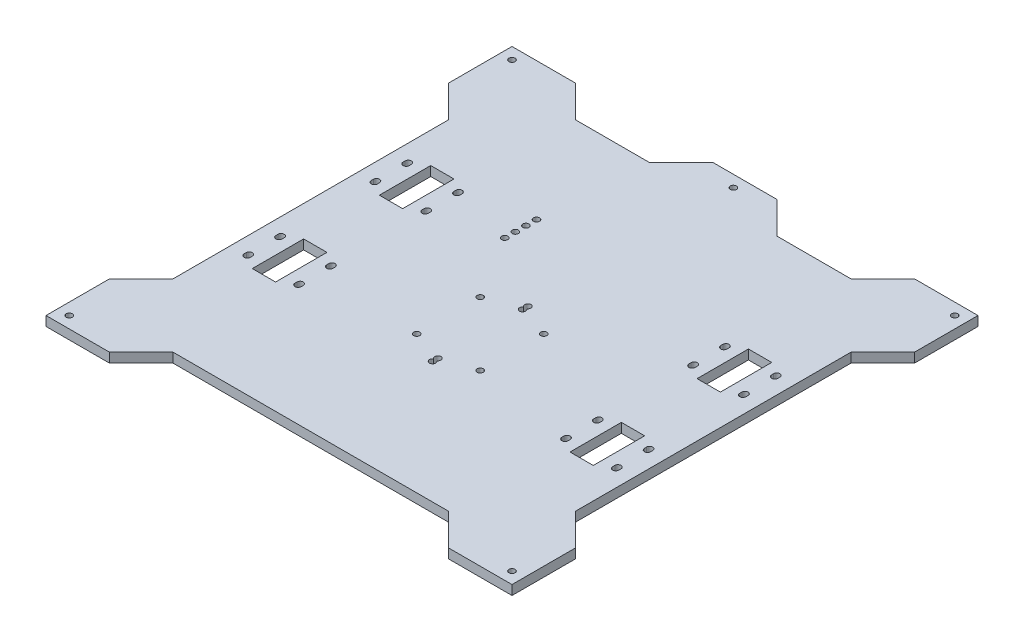
SolidWorks part; units mm, degrees
ref_plane "Front Plane" through (0, 0, 0) normal (0, 0, 1) x (1, 0, 0)
ref_plane "Top Plane" through (0, 0, 0) normal (0, 1, 0) x (1, 0, 0)
ref_plane "Right Plane" through (0, 0, 0) normal (1, 0, 0) x (0, 0, -1)
sketch "Sketch1" plane through (0, 0, 0) normal (0, 1, 0) x (1, 0, 0)
  line L1 (-110, 110) -> (110, 110)
  line L2 (-110, 110) -> (-110, -110)
  line L3 (-110, -110) -> (110, -110)
  line L4 (110, 110) -> (110, -110)
  line L5 (-110, 110) -> (110, -110) construction
  line L6 (-110, -110) -> (110, 110) construction
  point P0 (0, 0)
  dimension "D1" = 220
  dimension "D2" = 220
extrude "Square" add sketch "Sketch1" along normal blind 4.5
sketch "Sketch2" plane through (0, 4.5, 0) normal (0, 1, 0) x (1, 0, 0)
  line L0 (0, 110) -> (0, -110) construction
  line L1 (110, 110) -> (-110, 110) construction
  line L2 (-110, -110) -> (110, -110) construction
  line L3 (-110, 0) -> (110, 0) construction
  line L4 (-110, 110) -> (-110, -110) construction
  line L5 (110, -110) -> (110, 110) construction
  line L6 (75, 110) -> (75, -110) construction
  line L7 (75, 30) -> (0, 30) construction
  line L8 (75, -30) -> (0, -30) construction
  circle A0 centre (87, 38) radius 1.45
  circle A1 centre (87, 22) radius 1.45
  circle A2 centre (63, 22) radius 1.45
  circle A3 centre (63, 38) radius 1.45
  circle A4 centre (-63, 38) radius 1.45
  circle A5 centre (-63, 22) radius 1.45
  circle A6 centre (-87, 22) radius 1.45
  circle A7 centre (-87, 38) radius 1.45
  circle A8 centre (-87, 22) radius 1.45
  circle A9 centre (-87, 38) radius 1.45
  circle A10 centre (-63, 38) radius 1.45
  circle A11 centre (-63, 22) radius 1.45
  circle A12 centre (63, 22) radius 1.45
  circle A13 centre (63, 38) radius 1.45
  circle A14 centre (87, 38) radius 1.45
  circle A15 centre (87, 22) radius 1.45
  circle A16 centre (87, -22) radius 1.45
  circle A17 centre (87, -38) radius 1.45
  circle A18 centre (63, -38) radius 1.45
  circle A19 centre (63, -22) radius 1.45
  circle A20 centre (-63, -22) radius 1.45
  circle A21 centre (-63, -38) radius 1.45
  circle A22 centre (-87, -38) radius 1.45
  circle A23 centre (-87, -22) radius 1.45
  circle A24 centre (-87, -38) radius 1.45
  circle A25 centre (-87, -22) radius 1.45
  circle A26 centre (-63, -22) radius 1.45
  circle A27 centre (-63, -38) radius 1.45
  circle A28 centre (63, -38) radius 1.45
  circle A29 centre (63, -22) radius 1.45
  circle A30 centre (87, -22) radius 1.45
  circle A31 centre (87, -38) radius 1.45
  dimension "D6" = 2.9
  dimension "D7" = 2.9
  dimension "D1" = 75
  dimension "D2" = 30
  dimension "D3" = 16
  dimension "D5" = 12
extrude "LM8UU-Holders" cut sketch "Sketch2" against normal through all contours A7 | A6 | A5 | A4 | A20 | A21 | A22 | A23 | A19 | A18 | A17 | A16 | A1 | A0 | A3 | A2 region at (87, 4.5, -38) region at (87, 4.5, -22) region at (63, 4.5, -22) region at (63, 4.5, -38) region at (-63, 4.5, -38) region at (-63, 4.5, -22) region at (-87, 4.5, -22) region at (-87, 4.5, -38) region at (87, 4.5, 22) region at (87, 4.5, 38) region at (63, 4.5, 38) region at (63, 4.5, 22) region at (-63, 4.5, 22) region at (-63, 4.5, 38) region at (-87, 4.5, 38) region at (-87, 4.5, 22)
sketch "Sketch10" plane through (0, 4.5, 0) normal (0, 1, 0) x (1, 0, 0)
  line L0 (0, 110) -> (0, -79.9796) construction
  line L3 (-26.5242, 0) -> (110, 0) construction
  line L6 (75, 110) -> (75, -110) construction
  line L7 (75, 30) -> (-75, 30) construction
  line L8 (87, 22) -> (87, 23) construction
  line L9 (110, 110) -> (-110, 110) construction
  line L10 (110, -110) -> (110, 110) construction
  line L11 (85.55, 22) -> (85.55, 23)
  line L12 (88.45, 22) -> (88.45, 23)
  line L13 (87, 38) -> (87, 37) construction
  line L14 (88.45, 38) -> (88.45, 37)
  line L15 (85.55, 38) -> (85.55, 37)
  line L16 (63, 38) -> (63, 37) construction
  line L17 (61.55, 38) -> (61.55, 37)
  line L18 (64.45, 38) -> (64.45, 37)
  line L19 (63, 22) -> (63, 23) construction
  line L20 (64.45, 22) -> (64.45, 23)
  line L21 (61.55, 22) -> (61.55, 23)
  line L22 (75, -30) -> (-75, -30) construction
  line L23 (87, -22) -> (87, -23) construction
  line L24 (85.55, -22) -> (85.55, -23)
  line L25 (88.45, -22) -> (88.45, -23)
  line L26 (87, -38) -> (87, -37) construction
  line L27 (88.45, -38) -> (88.45, -37)
  line L28 (85.55, -38) -> (85.55, -37)
  line L29 (63, -38) -> (63, -37) construction
  line L30 (61.55, -38) -> (61.55, -37)
  line L31 (64.45, -38) -> (64.45, -37)
  line L32 (63, -22) -> (63, -23) construction
  line L33 (64.45, -22) -> (64.45, -23)
  line L34 (61.55, -22) -> (61.55, -23)
  line L35 (26.5242, 0) -> (-110, 0) construction
  line L36 (-87, 22) -> (-87, 23) construction
  line L37 (-85.55, 22) -> (-85.55, 23)
  line L38 (-88.45, 22) -> (-88.45, 23)
  line L39 (-87, 38) -> (-87, 37) construction
  line L40 (-88.45, 38) -> (-88.45, 37)
  line L41 (-85.55, 38) -> (-85.55, 37)
  line L42 (-63, 38) -> (-63, 37) construction
  line L43 (-61.55, 38) -> (-61.55, 37)
  line L44 (-64.45, 38) -> (-64.45, 37)
  line L45 (-63, 22) -> (-63, 23) construction
  line L46 (-64.45, 22) -> (-64.45, 23)
  line L47 (-61.55, 22) -> (-61.55, 23)
  line L48 (-87, -22) -> (-87, -23) construction
  line L49 (-85.55, -22) -> (-85.55, -23)
  line L50 (-88.45, -22) -> (-88.45, -23)
  line L51 (-87, -38) -> (-87, -37) construction
  line L52 (-88.45, -38) -> (-88.45, -37)
  line L53 (-85.55, -38) -> (-85.55, -37)
  line L54 (-63, -38) -> (-63, -37) construction
  line L55 (-61.55, -38) -> (-61.55, -37)
  line L56 (-64.45, -38) -> (-64.45, -37)
  line L57 (-63, -22) -> (-63, -23) construction
  line L58 (-64.45, -22) -> (-64.45, -23)
  line L59 (-61.55, -22) -> (-61.55, -23)
  arc A0 (61.55, 38) -> (64.45, 38) centre (63, 38) cw
  arc A1 (88.45, 38) -> (85.55, 38) centre (87, 38) ccw
  arc A2 (85.55, 22) -> (88.45, 22) centre (87, 22) ccw
  arc A3 (88.45, 23) -> (85.55, 23) centre (87, 23) ccw
  arc A4 (85.55, 37) -> (88.45, 37) centre (87, 37) ccw
  arc A5 (64.45, 37) -> (61.55, 37) centre (63, 37) cw
  arc A6 (64.45, 22) -> (61.55, 22) centre (63, 22) cw
  arc A7 (61.55, 23) -> (64.45, 23) centre (63, 23) cw
  arc A8 (85.55, -22) -> (88.45, -22) centre (87, -22) cw
  arc A9 (88.45, -23) -> (85.55, -23) centre (87, -23) cw
  arc A10 (88.45, -38) -> (85.55, -38) centre (87, -38) cw
  arc A11 (85.55, -37) -> (88.45, -37) centre (87, -37) cw
  arc A12 (61.55, -38) -> (64.45, -38) centre (63, -38) ccw
  arc A13 (64.45, -37) -> (61.55, -37) centre (63, -37) ccw
  arc A14 (64.45, -22) -> (61.55, -22) centre (63, -22) ccw
  arc A15 (61.55, -23) -> (64.45, -23) centre (63, -23) ccw
  arc A16 (-85.55, 22) -> (-88.45, 22) centre (-87, 22) cw
  arc A17 (-88.45, 23) -> (-85.55, 23) centre (-87, 23) cw
  arc A18 (-88.45, 38) -> (-85.55, 38) centre (-87, 38) cw
  arc A19 (-85.55, 37) -> (-88.45, 37) centre (-87, 37) cw
  arc A20 (-61.55, 38) -> (-64.45, 38) centre (-63, 38) ccw
  arc A21 (-64.45, 37) -> (-61.55, 37) centre (-63, 37) ccw
  arc A22 (-64.45, 22) -> (-61.55, 22) centre (-63, 22) ccw
  arc A23 (-61.55, 23) -> (-64.45, 23) centre (-63, 23) ccw
  arc A24 (-85.55, -22) -> (-88.45, -22) centre (-87, -22) ccw
  arc A25 (-88.45, -23) -> (-85.55, -23) centre (-87, -23) ccw
  arc A26 (-88.45, -38) -> (-85.55, -38) centre (-87, -38) ccw
  arc A27 (-85.55, -37) -> (-88.45, -37) centre (-87, -37) ccw
  arc A28 (-61.55, -38) -> (-64.45, -38) centre (-63, -38) cw
  arc A29 (-64.45, -37) -> (-61.55, -37) centre (-63, -37) cw
  arc A30 (-64.45, -22) -> (-61.55, -22) centre (-63, -22) cw
  arc A31 (-61.55, -23) -> (-64.45, -23) centre (-63, -23) cw
  point P8 (87, 22.5)
  point P19 (87, 37.5)
  point P28 (63, 37.5)
  point P35 (63, 22.5)
  point P44 (87, -22.5)
  point P51 (87, -37.5)
  point P58 (63, -37.5)
  point P65 (63, -22.5)
  point P73 (0, 30)
  point P74 (0, -30)
  point P76 (-87, 22.5)
  point P83 (-87, 37.5)
  point P90 (-63, 37.5)
  point P97 (-63, 22.5)
  point P104 (-87, -22.5)
  point P111 (-87, -37.5)
  point P118 (-63, -37.5)
  point P125 (-63, -22.5)
  dimension "D1" = 75
  dimension "D2" = 30
  dimension "D3" = 16
  dimension "D5" = 12
  dimension "D4" = 1.45
  dimension "D7" = 1.45
  dimension "D8" = 1
  dimension "D9" = 1
sketch "Sketch3" plane through (0, 4.5, 0) normal (0, 1, 0) x (1, 0, 0)
  line L0 (0, -110) -> (0, 110) construction
  line L1 (-110, -110) -> (110, -110) construction
  line L2 (110, 110) -> (-110, 110) construction
  line L3 (110, -15) -> (-110, -15) construction
  line L6 (15, -30) -> (-15, -30) construction
  line L7 (15, 0) -> (-15, 0) construction
  line L8 (110, -110) -> (110, 110) construction
  line L9 (-110, 110) -> (-110, -110) construction
  line L10 (110, 0) -> (-110, 0) construction
  circle A0 centre (-15, -30) radius 1.45
  circle A1 centre (15, -30) radius 1.45
  circle A2 centre (15, 0) radius 1.45
  circle A3 centre (-15, 0) radius 1.45
  point P16 (0, -30)
  dimension "D1" = 2.9
  dimension "D2" = 15
  dimension "D3" = 15
  dimension "D5" = 15
extrude "DefaultBelt" cut sketch "Sketch3" against normal through all
sketch "Sketch4" plane through (0, 4.5, 0) normal (0, 1, 0) x (1, 0, 0)
  line L0 (0, 110) -> (0, -110) construction
  line L1 (110, 110) -> (-110, 110) construction
  line L2 (-110, -110) -> (110, -110) construction
  line L3 (-15, -1.45) -> (-15, -28.55) construction
  line L4 (15, -28.55) -> (15, -1.45) construction
  line L5 (15, -15) -> (-15, -15) construction
  arc A0 (-0.7348, 6.25) -> (0.7348, 6.25) centre (0, 5) ccw
  arc A1 (0.7348, 6.25) -> (-0.7348, 6.25) centre (0, 7.5) ccw
  arc A2 (0.7348, -36.25) -> (-0.7348, -36.25) centre (0, -37.5) cw
  arc A3 (-0.7348, -36.25) -> (0.7348, -36.25) centre (0, -35) cw
  circle A4 centre (-15, 0) radius 1.45 construction
  circle A5 centre (-15, -30) radius 1.45 construction
  circle A6 centre (15, -30) radius 1.45 construction
  circle A7 centre (15, 0) radius 1.45 construction
  dimension "D1" = 2.9
  dimension "D2" = 2.9
  dimension "D3" = 20
  dimension "D4" = 22.5
extrude "BeltOptions" cut sketch "Sketch4" against normal through all
sketch "Sketch5" plane through (0, 4.5, 0) normal (0, 1, 0) x (1, 0, 0)
  line L0 (-110, 0) -> (110, 0) construction
  line L1 (-110, 110) -> (-110, -110) construction
  line L2 (110, -110) -> (110, 110) construction
  line L3 (0, 110) -> (0, -110) construction
  line L4 (110, 110) -> (-110, 110) construction
  line L5 (-110, 110) -> (-110, 80)
  line L6 (-110, 80) -> (-95, 65)
  line L7 (-95, 65) -> (-95, -65)
  line L8 (0, 0) -> (-110, 110) construction
  line L9 (-65, 95) -> (65, 95)
  line L10 (-80, 110) -> (-65, 95)
  line L11 (-110, 110) -> (-80, 110)
  line L12 (-95, 65) -> (-95, -65)
  line L13 (0, 0) -> (110, 110) construction
  line L14 (95, 65) -> (95, -65)
  line L15 (110, 110) -> (80, 110)
  line L16 (80, 110) -> (65, 95)
  line L17 (95, 65) -> (95, -65)
  line L18 (110, 80) -> (95, 65)
  line L19 (110, 110) -> (110, 80)
  line L20 (0, 0) -> (110, -110) construction
  line L21 (0, 0) -> (-110, -110) construction
  line L22 (110, -110) -> (110, -80)
  line L23 (110, -80) -> (95, -65)
  line L24 (80, -110) -> (65, -95)
  line L25 (110, -110) -> (80, -110)
  line L26 (-110, -110) -> (-80, -110)
  line L27 (-80, -110) -> (-65, -95)
  line L28 (-65, -95) -> (65, -95)
  line L29 (-110, -80) -> (-95, -65)
  line L30 (-110, -110) -> (-110, -80)
  point P24 (0, 95)
  point P32 (95, 0)
  point P35 (-95, 0)
  point P36 (0, -95)
  circle M16 centre (15, -30) radius 1.45
  circle M18 centre (63, 38) radius 1.45
  circle M20 centre (87, 22) radius 1.45
  circle M22 centre (87, -38) radius 1.45
  circle M23 centre (63, -38) radius 1.45
  circle M24 centre (63, -22) radius 1.45
  circle M25 centre (-87, -22) radius 1.45
  circle M26 centre (-87, -38) radius 1.45
  circle M27 centre (-63, -38) radius 1.45
  circle M28 centre (-63, -22) radius 1.45
  circle M29 centre (-63, 38) radius 1.45
  circle M30 centre (-63, 22) radius 1.45
  circle M31 centre (-87, 22) radius 1.45
  circle M32 centre (-87, 38) radius 1.45
  line M33 (110, -110) -> (110, 110)
  line M34 (110, 110) -> (-110, 110)
  line M35 (-110, 110) -> (-110, -110)
  line M36 (-110, -110) -> (110, -110)
  dimension "D1" = 15
  dimension "D2" = 30
  dimension "D3" = 45
  dimension "D4" = 45
extrude "Shaping" cut sketch "Sketch5" against normal blind 10 flip side to cut contours L29 L27 L28 L24 L23 L14 L18 L16 L9 L10 L6 L7 M35 M36 M33 M34 M16 M18 M20 M22 M24 M26 M28 M30 M32 M31 M29 M27 M25 M23 region at (0.037, 4.5, -0.0113)
sketch "Sketch6" plane through (0, 4.5, 0) normal (0, 1, 0) x (1, 0, 0)
  line L0 (-110, 110) -> (110, -110) construction
  line L1 (-110, -110) -> (110, 110) construction
  line L2 (110, 80) -> (110, 110) construction
  line L3 (0, 95) -> (0, -95) construction
  line L4 (-65, 95) -> (65, 95) construction
  line L5 (-65, -95) -> (65, -95) construction
  line L6 (-95, 0) -> (95, 0) construction
  line L7 (-95, 65) -> (-95, -65) construction
  line L8 (95, 65) -> (95, -65) construction
  circle A0 centre (-104.5, 104.5) radius 1.45
  circle A1 centre (104.5, 104.5) radius 1.45
  circle A2 centre (104.5, -104.5) radius 1.45
  circle A3 centre (-104.5, -104.5) radius 1.45
  dimension "D2" = 2.9
  dimension "D1" = 45
  dimension "D3" = 104.5
extrude "Cut-Extrude5" cut sketch "Sketch6" against normal through all
sketch "Sketch7" plane through (0, 4.5, 0) normal (0, 1, 0) x (1, 0, 0)
  line L0 (-87, 38) -> (-63, 22) construction
  line L1 (-63, 22) -> (-87, 22) construction
  line L2 (-87, 22) -> (-63, 38) construction
  line L3 (-63, 38) -> (-87, 38) construction
  line L4 (-95, 0) -> (95, 0) construction
  line L5 (-80.5, 42.125) -> (-69.5, 42.125)
  line L6 (-80.5, 42.125) -> (-80.5, 17.875)
  line L7 (-80.5, 17.875) -> (-69.5, 17.875)
  line L8 (-69.5, 42.125) -> (-69.5, 17.875)
  line L9 (-80.5, 42.125) -> (-69.5, 17.875) construction
  line L10 (-80.5, 17.875) -> (-69.5, 42.125) construction
  line L11 (-95, 65) -> (-95, -65) construction
  line L12 (95, 65) -> (95, -65) construction
  line L13 (0, -95) -> (0, 95) construction
  line L14 (-65, -95) -> (65, -95) construction
  line L15 (-65, 95) -> (65, 95) construction
  line L16 (-80.5, -17.875) -> (-69.5, -42.125) construction
  line L17 (-80.5, -42.125) -> (-69.5, -17.875) construction
  line L18 (-63, -38) -> (-87, -38) construction
  line L19 (-87, -22) -> (-63, -38) construction
  line L20 (-63, -22) -> (-87, -22) construction
  line L21 (-87, -38) -> (-63, -22) construction
  line L22 (-69.5, -42.125) -> (-69.5, -17.875)
  line L23 (-80.5, -17.875) -> (-69.5, -17.875)
  line L24 (-80.5, -42.125) -> (-80.5, -17.875)
  line L25 (-80.5, -42.125) -> (-69.5, -42.125)
  line L26 (-80.5, 17.875) -> (-69.5, 42.125) construction
  line L27 (80.5, 17.875) -> (69.5, 42.125) construction
  line L28 (87, -38) -> (63, -22) construction
  line L29 (63, -22) -> (87, -22) construction
  line L30 (87, -22) -> (63, -38) construction
  line L31 (63, -38) -> (87, -38) construction
  line L32 (80.5, -42.125) -> (69.5, -17.875) construction
  line L33 (80.5, -17.875) -> (69.5, -42.125) construction
  line L34 (80.5, 17.875) -> (69.5, 42.125) construction
  line L35 (80.5, 42.125) -> (69.5, 17.875) construction
  line L36 (63, 38) -> (87, 38) construction
  line L37 (87, 22) -> (63, 38) construction
  line L38 (63, 22) -> (87, 22) construction
  line L39 (87, 38) -> (63, 22) construction
  line L40 (80.5, -42.125) -> (69.5, -42.125)
  line L41 (80.5, -42.125) -> (80.5, -17.875)
  line L42 (80.5, -17.875) -> (69.5, -17.875)
  line L43 (69.5, -42.125) -> (69.5, -17.875)
  line L44 (69.5, 42.125) -> (69.5, 17.875)
  line L45 (80.5, 17.875) -> (69.5, 17.875)
  line L46 (80.5, 42.125) -> (80.5, 17.875)
  line L47 (80.5, 42.125) -> (69.5, 42.125)
  point P4 (-75, 30)
  point P33 (-75, -30)
  point P50 (75, -30)
  point P51 (75, 30)
  dimension "D1" = 11
  dimension "D2" = 24.25
extrude "Cut-Extrude6" cut sketch "Sketch7" against normal through all
sketch "Sketch8" plane through (0, 4.5, 0) normal (0, 1, 0) x (1, 0, 0)
  line L3 (-65, 95) -> (65, 95) construction
  line L4 (-33.45, 45) -> (-33.45, 30) construction
  circle A0 centre (-33.45, 45) radius 1.45
  circle A1 centre (-33.45, 40) radius 1.45
  circle A2 centre (-33.45, 35) radius 1.45
  circle A3 centre (-33.45, 30) radius 1.45
  dimension "D1" = 2.9
  dimension "D2" = 50
  dimension "D4" = 33.45
extrude "EndstopTrigger" cut sketch "Sketch8" against normal through all
pattern_linear "LPattern1" [suppressed] count 2 spacing 30 of bodies 108
sketch "Sketch9" plane through (0, 4.5, 0) normal (0, 1, 0) x (1, 0, 0)
  line L0 (-80, 110) -> (-110, 110) construction
  line L1 (-65, 95) -> (65, 95) construction
  line L7 (-95, 0) -> (95, 0) construction
  line L8 (-95, 65) -> (-95, -65) construction
  line L11 (95, 65) -> (95, -65) construction
  line L12 (-104.5, 104.5) -> (104.5, 104.5) construction
  line L13 (0, 110) -> (0, 95) construction
  line L14 (-80, 110) -> (80, 110) construction
  line L15 (15, 110) -> (30, 95)
  line L16 (-30, 95) -> (30, 95)
  line L17 (-15, 110) -> (-30, 95)
  line L18 (15, 110) -> (-15, 110)
  circle A1 centre (0, 104.5) radius 1.45
  dimension "D2" = 30
  dimension "D3" = 2.9
  dimension "D1" = 45
  dimension "D4" = 45
extrude "Boss-Extrude1" add sketch "Sketch9" against normal through all
extrude "HolesToSlots" cut sketch "Sketch10" against normal through all
sketch "Sketch11" plane through (0, 4.5, 0) normal (0, 1, 0) x (1, 0, 0)
  line L0 (0, -95) -> (0, 0) construction
  line L1 (-65, -95) -> (65, -95) construction
  line L2 (95, 0) -> (0, 0) construction
  line L3 (95, 65) -> (95, -65) construction
  line L4 (0, 0) -> (110, -110) construction
  line L5 (-69.1421, -85) -> (-5, -85)
  line L6 (-69.1421, -85) -> (-84.1421, -100)
  line L7 (-84.1421, -100) -> (-100, -100)
  line L8 (-100, -100) -> (-100, -84.1421)
  line L9 (-100, -84.1421) -> (-85, -69.1421)
  line L10 (-85, -69.1421) -> (-85, -52.125)
  line L11 (-85, -52.125) -> (-5, -52.125)
  line L12 (-80, -110) -> (-65, -95) construction
  line L13 (-110, -80) -> (-95, -65) construction
  line L14 (-110, -80) -> (-110, -110) construction
  line L15 (-110, -110) -> (-80, -110) construction
  line L16 (-80.5, -42.125) -> (-69.5, -42.125) construction
  line L17 (-95, 65) -> (-95, -65) construction
  line L18 (-5, -52.125) -> (-5, -85)
  line L19 (5, -52.125) -> (5, -85)
  line L20 (85, -52.125) -> (5, -52.125)
  line L21 (85, -69.1421) -> (85, -52.125)
  line L22 (100, -84.1421) -> (85, -69.1421)
  line L23 (100, -100) -> (100, -84.1421)
  line L24 (84.1421, -100) -> (100, -100)
  line L25 (69.1421, -85) -> (84.1421, -100)
  line L26 (69.1421, -85) -> (5, -85)
  line L27 (69.1421, 85) -> (5, 85)
  line L28 (69.1421, 85) -> (84.1421, 100)
  line L29 (84.1421, 100) -> (100, 100)
  line L30 (100, 100) -> (100, 84.1421)
  line L31 (100, 84.1421) -> (85, 69.1421)
  line L32 (85, 69.1421) -> (85, 52.125)
  line L33 (85, 52.125) -> (5, 52.125)
  line L34 (5, 52.125) -> (5, 85)
  line L35 (-5, 52.125) -> (-5, 85)
  line L36 (-85, 52.125) -> (-5, 52.125)
  line L37 (-85, 69.1421) -> (-85, 52.125)
  line L38 (-100, 84.1421) -> (-85, 69.1421)
  line L39 (-100, 100) -> (-100, 84.1421)
  line L40 (-84.1421, 100) -> (-100, 100)
  line L41 (-69.1421, 85) -> (-84.1421, 100)
  line L42 (-69.1421, 85) -> (-5, 85)
  dimension "D1" = 10
  dimension "D2" = 10
  dimension "D3" = 10
  dimension "D4" = 10
  dimension "D5" = 10
  dimension "D6" = 10
  dimension "D7" = 10
  dimension "D8" = 5
extrude "Cut-Extrude7" [suppressed] cut sketch "Sketch11" against normal through all
sketch "Sketch12" [suppressed] plane through (0, 4.5, 0) normal (0, 1, 0) x (1, 0, 0)
  line L0 (0, 0) -> (-110, -110) construction
  line L1 (-110, -110) -> (-80, -110) construction
  line L2 (-110, -80) -> (80, 110) construction
  line L3 (110, 80) -> (-80, -110) construction
  line L4 (-95, -65) -> (-65, -95) construction
  line L5 (0, 0) -> (0, -95) construction
  line L6 (-65, -95) -> (65, -95) construction
  line L7 (95, 0) -> (-95, 0) construction
  line L8 (-95, 65) -> (-95, -65) construction
  line L9 (-100, -100) -> (-100, -84.1421)
  line L10 (-100, -84.1421) -> (-59.2893, -43.4315)
  line L11 (-59.2893, -43.4315) -> (-43.4315, -43.4315)
  line L12 (-110, -80) -> (-110, -110) construction
  line L13 (-100, -100) -> (-84.1421, -100)
  line L14 (-84.1421, -100) -> (-43.4315, -59.2893)
  line L15 (-43.4315, -59.2893) -> (-43.4315, -43.4315)
  line L16 (55, -85) -> (-55, -85)
  line L17 (-55, -85) -> (-29.2893, -59.2893)
  line L18 (-29.2893, -59.2893) -> (29.2893, -59.2893)
  line L19 (95, -65) -> (65, -95) construction
  line L20 (0, 0) -> (110, -110) construction
  line L21 (55, -85) -> (29.2893, -59.2893)
  line L22 (43.4315, -59.2893) -> (43.4315, -43.4315)
  line L23 (84.1421, -100) -> (43.4315, -59.2893)
  line L24 (100, -100) -> (84.1421, -100)
  line L25 (59.2893, -43.4315) -> (43.4315, -43.4315)
  line L26 (100, -84.1421) -> (59.2893, -43.4315)
  line L27 (100, -100) -> (100, -84.1421)
  line L28 (95, 65) -> (65, 95) construction
  line L29 (-95, 65) -> (-65, 95) construction
  line L30 (100, 100) -> (100, 84.1421)
  line L31 (100, 84.1421) -> (59.2893, 43.4315)
  line L32 (59.2893, 43.4315) -> (43.4315, 43.4315)
  line L33 (100, 100) -> (84.1421, 100)
  line L34 (84.1421, 100) -> (43.4315, 59.2893)
  line L35 (43.4315, 59.2893) -> (43.4315, 43.4315)
  line L36 (55, 85) -> (29.2893, 59.2893)
  line L37 (-29.2893, 59.2893) -> (29.2893, 59.2893)
  line L38 (-55, 85) -> (-29.2893, 59.2893)
  line L39 (55, 85) -> (-55, 85)
  line L40 (-43.4315, 59.2893) -> (-43.4315, 43.4315)
  line L41 (-84.1421, 100) -> (-43.4315, 59.2893)
  line L42 (-100, 100) -> (-84.1421, 100)
  line L43 (-59.2893, 43.4315) -> (-43.4315, 43.4315)
  line L44 (-100, 84.1421) -> (-59.2893, 43.4315)
  line L45 (-100, 100) -> (-100, 84.1421)
  point P40 (0, -59.2893)
  point P41 (0, -85)
  point P67 (0, 85)
  point P68 (0, 59.2893)
  dimension "D1" = 10
  dimension "D2" = 10
  dimension "D3" = 80
  dimension "D4" = 10
  dimension "D5" = 10
  dimension "D6" = 0
extrude "Cut-Extrude8" [suppressed] cut sketch "Sketch12" against normal through all
sketch "Sketch14" [suppressed] plane through (0, 4.5, 0) normal (0, 1, 0) x (1, 0, 0)
  line L0 (0, 85) -> (0, 110) construction
  line L1 (55, 85) -> (-55, 85) construction
  line L2 (15, 110) -> (-15, 110) construction
  line L3 (10.8579, 100) -> (-10.8579, 100)
  line L4 (-10.8579, 100) -> (-25.8579, 85)
  line L5 (-25.8579, 85) -> (25.8579, 85)
  line L6 (-15, 110) -> (-30, 95) construction
  line L7 (10.8579, 100) -> (25.8579, 85)
  point P13 (0, 100)
  dimension "D1" = 10
  dimension "D2" = 10
extrude "Cut-Extrude10" [suppressed] cut sketch "Sketch14" against normal through all
sketch "Sketch13" [suppressed] plane through (0, 4.5, 0) normal (0, 1, 0) x (1, 0, 0)
  line L0 (-59.2893, 43.4315) -> (-59.2893, -43.4315) construction
  line L1 (-100, 84.1421) -> (-59.2893, 43.4315) construction
  line L2 (-59.2893, 0) -> (0, 0) construction
  line L3 (-59.2893, 33.4315) -> (-59.2893, -33.4315)
  line L4 (-59.2893, -33.4315) -> (-43.4315, -33.4315)
  line L5 (-43.4315, -33.4315) -> (-43.4315, 33.4315)
  line L6 (-43.4315, 33.4315) -> (-59.2893, 33.4315)
  line L7 (-59.2893, 43.4315) -> (-43.4315, 43.4315) construction
  line L8 (-43.4315, -43.4315) -> (-59.2893, -43.4315) construction
  line L9 (-43.4315, 43.4315) -> (-43.4315, 59.2893) construction
  line L10 (0, 0) -> (0, 43.4315) construction
  line L11 (59.2893, 43.4315) -> (59.2893, -43.4315) construction
  line L12 (43.4315, 33.4315) -> (59.2893, 33.4315)
  line L13 (43.4315, -33.4315) -> (43.4315, 33.4315)
  line L14 (59.2893, -33.4315) -> (43.4315, -33.4315)
  line L15 (59.2893, 33.4315) -> (59.2893, -33.4315)
  line L16 (110, -110) -> (0, 0) construction
  line L17 (55, -85) -> (29.2893, -59.2893) construction
  line L18 (-33.4315, -43.2893) -> (33.4315, -43.2893)
  line L19 (-33.4315, -43.2893) -> (-33.4315, -63.4315)
  line L20 (-33.4315, -63.4315) -> (33.4315, -63.4315)
  line L21 (33.4315, -43.2893) -> (33.4315, -63.4315)
  line L22 (-33.4315, -43.2893) -> (33.4315, -63.4315) construction
  line L23 (-33.4315, -63.4315) -> (33.4315, -43.2893) construction
  line L24 (-43.4315, -59.2893) -> (-43.4315, -43.4315) construction
  line L25 (0, -53.3604) -> (0, -63.4315) construction
  line L26 (55, 85) -> (25.8579, 85) construction
  line L28 (43.4315, -43.4315) -> (43.4315, -59.2893) construction
  line L29 (29.2893, -59.2893) -> (-29.2893, -59.2893) construction
  line L30 (43.4315, 59.2893) -> (43.4315, 43.4315) construction
  line L31 (-33.4315, 83) -> (33.4315, 83)
  line L32 (-33.4315, 83) -> (-33.4315, 15)
  line L33 (-33.4315, 15) -> (33.4315, 15)
  line L34 (33.4315, 83) -> (33.4315, 15)
  line L35 (-33.4315, 83) -> (33.4315, 15) construction
  line L36 (-33.4315, 15) -> (33.4315, 83) construction
  point P27 (0, -53.3604)
  point P43 (0, 49)
  point P50 (0, 0)
  dimension "D1" = 10
  dimension "D2" = 10
  dimension "D3" = 10
  dimension "D4" = 10
  dimension "D5" = 16
  dimension "D6" = 10
  dimension "D7" = 10
  dimension "D8" = 15
  dimension "D9" = 2
extrude "Cut-Extrude9" [suppressed] cut sketch "Sketch13" against normal through all
sketch "Sketch15" [suppressed] plane through (0, 4.5, 0) normal (0, 1, 0) x (1, 0, 0)
  line L0 (-59.2893, 0) -> (-95, 0) construction
  line L1 (-59.2893, 33.4315) -> (-59.2893, -33.4315) construction
  line L2 (-95, 65) -> (-95, -65) construction
  line L3 (-80.5, 17.875) -> (-69.5, 17.875) construction
  line L4 (-59.2893, -15) -> (-59.2893, -7.875)
  line L5 (-85, -7.875) -> (-85, 7.875)
  line L6 (-85, 7.875) -> (-66.4143, 7.875)
  line L7 (-59.2893, -7.875) -> (-59.2893, 7.875)
  line L8 (-66.4143, -7.875) -> (-59.2893, -15)
  line L9 (-85, -7.875) -> (-66.4143, -7.875)
  line L11 (-66.4143, 7.875) -> (-59.2893, 15)
  line L12 (-59.2893, 15) -> (-59.2893, 7.875)
  line L13 (0, 0) -> (0, -21.7485) construction
  line L14 (59.2893, 0) -> (95, 0) construction
  line L15 (59.2893, 15) -> (59.2893, 7.875)
  line L16 (66.4143, 7.875) -> (59.2893, 15)
  line L17 (85, -7.875) -> (66.4143, -7.875)
  line L18 (66.4143, -7.875) -> (59.2893, -15)
  line L19 (59.2893, -7.875) -> (59.2893, 7.875)
  line L20 (85, 7.875) -> (66.4143, 7.875)
  line L21 (85, -7.875) -> (85, 7.875)
  line L22 (59.2893, -15) -> (59.2893, -7.875)
  line L23 (-59.2893, 0) -> (-95, 0) construction
  point P17 (-85, 0)
  point P30 (85, 0)
  dimension "D1" = 10
  dimension "D2" = 10
  dimension "D4" = 45
  dimension "D5" = 15
extrude "Cut-Extrude11" [suppressed] cut sketch "Sketch15" against normal through all
sketch "Sketch16" [suppressed] plane through (0, 4.5, 0) normal (0, 1, 0) x (1, 0, 0)
  line L0 (-85, -69.1421) -> (-85, -52.125)
  line L1 (-59.2893, -43.4315) -> (-100, -84.1421) construction
  line L2 (-85, -52.125) -> (-67.9829, -52.125)
  line L3 (-67.9829, -52.125) -> (-85, -69.1421)
  line L4 (-95, 65) -> (-95, -65) construction
  line L5 (-80.5, -42.125) -> (-69.5, -42.125) construction
  line L6 (-95, 0) -> (95, 0) construction
  line L7 (95, 65) -> (95, -65) construction
  line L8 (0, 0) -> (0, -95) construction
  line L9 (-65, -95) -> (65, -95) construction
  line L10 (-67.9829, 52.125) -> (-85, 69.1421)
  line L11 (-85, 52.125) -> (-67.9829, 52.125)
  line L12 (-85, 69.1421) -> (-85, 52.125)
  line L13 (-67.9829, -52.125) -> (-85, -69.1421)
  line L14 (67.9829, -52.125) -> (85, -69.1421)
  line L15 (85, 69.1421) -> (85, 52.125)
  line L16 (85, 52.125) -> (67.9829, 52.125)
  line L17 (67.9829, 52.125) -> (85, 69.1421)
  line L18 (67.9829, -52.125) -> (85, -69.1421)
  line L19 (85, -52.125) -> (67.9829, -52.125)
  line L20 (85, -69.1421) -> (85, -52.125)
  line L21 (100, -84.1421) -> (59.2893, -43.4315) construction
  line L23 (69.5, -42.125) -> (80.5, -42.125) construction
  line L24 (80.5, 42.125) -> (69.5, 42.125) construction
  line L25 (59.2893, 43.4315) -> (100, 84.1421) construction
  line L26 (-100, 84.1421) -> (-59.2893, 43.4315) construction
  line L27 (-69.5, 42.125) -> (-80.5, 42.125) construction
  dimension "D1" = 10
  dimension "D2" = 10
  dimension "D3" = 10
  dimension "D4" = 10
  dimension "D5" = 10
  dimension "D6" = 10
  dimension "D7" = 10
  dimension "D8" = 10
extrude "Cut-Extrude12" [suppressed] cut sketch "Sketch16" against normal through all contours L3 L2 L0 | L10 L12 L11 | L17 L16 L15 | L14 L20 L19
equation "\"X-ROD-SPACING\"=45"
equation "\"Y-ROD-SPACING\"=75"
equation "\"Z-ROD-SPACING\"=17.5"
equation "\"Y-BED-OFFSET\"=2"
equation "\"Y-BED-ROD-INSET\"=3.5"
equation "\"T-SLOT-NUT-FILLET-RADIUS\"=0.5"
equation "\"T-SLOT-SCREW-SHAFT-RADIUS\"=1.55"
equation "\"T-SLOT-SCREW-SHAFT-CUTOUT-LENGTH\"=11.0"
equation "\"T-SLOT-NUT-DEPTH\"=3.5"
equation "\"T-SLOT-NUT-WIDTH\"=2.85"
equation "\"T-SLOT-NUT-END-DISTANCE\"=8"
equation "\"ACRYLIC-THICKNESS\"=10"
equation "\"ACRYLIC-THICKNESS2\"=4.5"
equation "\"ACRYLIC-TAB-CUTOUT-SIZE\"=\"ACRYLIC-THICKNESS\"+\"ACRYLIC-TAB-TOLERANCE\"*2"
equation "\"ACRYLIC-TAB-WIDTH\"=\"ACRYLIC-THICKNESS\""
equation "\"ACRYLIC-M3-HOLE\"=2.9"
equation "\"SMOOTHROD-CAP-SCREW-DISTANCE\"=20"
equation "\"FRAME-WIDTH-INNER\"=370"
equation "\"NEMA17-HOLE-SPACING\"=31"
equation "\"NEMA17-CENTRAL-CUTOUT\"=22.5"
equation "\"Z-BRACKET-REACH\"=55"
equation "\"TOP-BRACKET-SPACING\"=40"
equation "\"SMOOTHROD-X-LENGTH\"=350"
equation "\"SMOOTHROD-Y-LENGTH\"=350"
equation "\"SMOOTHROD-Z-LENGTH\"=350"
equation "\"SMOOTHROD-TIGHTENING-HEADROOM\"=.25"
equation "\"LEADSCREW-Z-LENGTH\"=300"
equation "\"SCREW-LENGTH-FRAME\"=\"ACRYLIC-THICKNESS\" + 10"
equation "\"SCREW-HEAD-RADIUS\"=6"
equation "\"PRINTED-X-SMOOTHROD-DIAMETER\"=9.0"
equation "\"PRINTED-X-SMOOTHROD-CUTOUT\"=10"
equation "\"PRINTED-X-BASE-HEIGHT\"=10"
equation "\"PRINTED-LM8UU-CUTOUT-SIZE\"=15.5"
equation "\"PRINTED-LM8UU-CUTOUT-LENGTH\"=24.5"
equation "\"PRINTED-X-IDLER-HEIGHT\"=16"
equation "\"PSU-MOUNTING-WIDTH\"=95"
equation "\"PSU-MOUNTING-HEIGHT\"=177"
equation "\"Y-BELT-TO-ROD-DISTANCE\"=20"
equation "\"D6@Sketch2\"=\"ACRYLIC-M3-HOLE\""
equation "\"D7@Sketch2\"=\"ACRYLIC-M3-HOLE\""
equation "\"D1@Sketch2\"=\"Y-ROD-SPACING\""
equation "\"D1@Sketch3\"=\"ACRYLIC-M3-HOLE\""
equation "\"D2@Sketch6\"=\"ACRYLIC-M3-HOLE\""
equation "\"Y-BED-SCREW-SPACING\"=209"
equation "\"Y-BED-SCREW-CUTOUT-SLOT-HEIGHT\"=2"
equation "\"ACRYLIC-TAB-TOLERANCE\"=-.05"
equation "\"Z-ROD-INSET\"=16"
equation "\"SCREW-LENGTH-MOTOR\"=\"ACRYLIC-THICKNESS\" + 5"
equation "\"SCREW-LENGTH-EXTRUDER\"=28"
equation "\"PRINTED-M3-HOLE\"=3.5"
equation "\"SPOOL-HOLDER-ROD-SPACING\"=150"
equation "\"ACRYLIC-X-CARRIAGE-WIDTH\"=55"
equation "\"ACRYLIC-X-CARRIAGE-HEIGHT\"=75"
equation "\"ACRYLIC-X-CARRIAGE-LM8UU-CUTOUT-WIDTH\"=24.25"
equation "\"ACRYLIC-X-CARRIAGE-LM8UU-CUTOUT-HEIGHT\"=11.0"
equation "\"ACRYLIC-X-CARRIAGE-SCREW-SPACING-X\"=15"
equation "\"ACRYLIC-X-CARRIAGE-SCREW-SPACING-Y\"=33"
equation "\"ACRYLIC-X-CARRIAGE-CENTER-TAB-SPACING\"=14"
equation "\"ACRYLIC-X-CARRIAGE-EXTRUDER-OFFSET\"=26"
equation "\"ACRYLIC-X-CARRIAGE-EXTRUDER-ANGLE\"=90"
equation "\"ACRYLIC-X-CARRIAGE-EXTRUDER-SHELF-DEPTH\"=\"ACRYLIC-X-CARRIAGE-EXTRUDER-OFFSET\" + 28"
equation "\"ACRYLIC-X-CARRIAGE-EXTRUDER-BRACE-SPACING\"=23"
equation "\"ACRYLIC-X-CARRIAGE-EXTRUDER-BRACE-TAB-OFFSET\"=20"
equation "\"ACRYLIC-X-CARRIAGE-EXTRUDER-BRACE-HEIGHT\"=35"
equation "\"ACRYLIC-X-CARRIAGE-EXTRUDER-BRACE-SCREW-SPACING\"=22"
equation "\"ACRYLIC-X-CARRIAGE-DUAL-WIDTH-MULTIPLIER\"=1.65"
equation "\"ACRYLIC-X-CARRIAGE-DUAL-HOTEND-SPACING\"=42"
equation "\"ACRYLIC-X-CARRIAGE-DUAL-WIDTH\"=75"
equation "\"ACRYLIC-X-CARRIAGE-DUAL-HOTEND-SEPARATION\"=36"
equation "\"ACRYLIC-X-CARRIAGE-DUAL-MOUNT-PLATE-DEPTH\"=75"
equation "\"ACRYLIC-X-CARRIAGE-DUAL-MOUNT-BRACE-WIDTH\"=33"
equation "\"ACRYLIC-X-CARRIAGE-DUAL-MOUNT-SCREW-WIDTH\"=40"
equation "\"BLOWER-FAN-WIDTH\"=15"
equation "\"D1@Sketch7\"=\"ACRYLIC-X-CARRIAGE-LM8UU-CUTOUT-HEIGHT\""
equation "\"D2@Sketch7\"=\"ACRYLIC-X-CARRIAGE-LM8UU-CUTOUT-WIDTH\""
equation "\"D1@Sketch8\"=\"ACRYLIC-M3-HOLE\""
equation "\"D2@Sketch4\"=\"ACRYLIC-M3-HOLE\""
equation "\"D1@Sketch4\"=\"ACRYLIC-M3-HOLE\""
equation "\"D3@Sketch4\"=20"
equation "\"D3@Sketch9\"=\"ACRYLIC-M3-HOLE\""
equation "\"D4@Sketch10\"=\"ACRYLIC-M3-HOLE\"/2"
equation "\"D7@Sketch10\"=\"ACRYLIC-M3-HOLE\" / 2"
